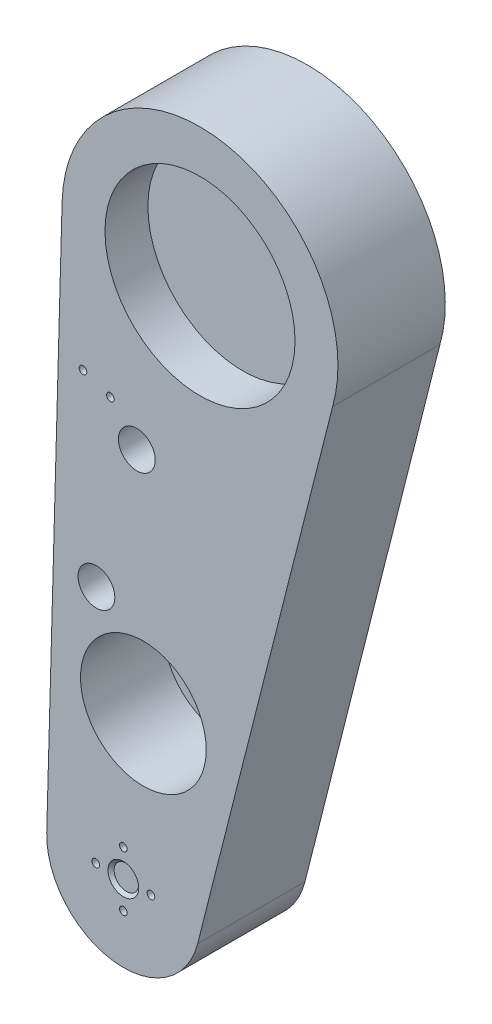
SolidWorks part; units mm, degrees
ref_plane "Ebene vorne" through (0, 0, 0) normal (0, 0, 1) x (1, 0, 0)
ref_plane "Ebene oben" through (0, 0, 0) normal (0, 1, 0) x (1, 0, 0)
ref_plane "Ebene rechts" through (0, 0, 0) normal (1, 0, 0) x (0, 0, -1)
sketch "Skizze1" plane through (0, 0, 0) normal (0, 0, 1) x (1, 0, 0)
  line L0 (-24.9904, 0.6931) -> (-19.9827, 181.2476)
  line L2 (68.9493, 170.3326) -> (24.2342, -6.1405)
  circle A0 centre (0, 0) radius 9
  circle A6 centre (0, 0) radius 25
  circle A7 centre (25, 180) radius 45
  circle A8 centre (25, 180) radius 28
  point P8 (0, 0)
  point P11 (-25, 0)
  point P12 (68.9493, 170.3326)
  point P14 (0, 0)
  dimension "D1" = 18
  dimension "D3" = 50
  dimension "D5" = 90
  dimension "D7" = 56
  dimension "D4" = 180
  dimension "D6" = 25
extrude "Aufsatz-Linear austragen1" add sketch "Skizze1" along normal blind 35 contours A7 | A7 A6 | A6 A0 | A0 | A7 region at (11.8715, 85.5396, 0) region at (0.3368, 24.2906, 0) region at (68.6084, 168.9504, 0) region at (0, 0, 0)
sketch "Skizze2" plane through (0, 0, 35) normal (0, 0, 1) x (1, 0, 0)
  circle A0 centre (0, 0) radius 4
  dimension "D1" = 8
extrude "Schnitt-Linear austragen1" cut sketch "Skizze2" against normal blind 1 contours A0
chamfer "Fase1" distance 1 angle 45 1 edges at (4, 0, 35)
sketch "Skizze3" plane through (0, 0, 35) normal (0, 0, 1) x (1, 0, 0)
sketch "Skizze4" plane through (0, 0, 35) normal (0, 0, 1) x (1, 0, 0)
  arc A0 (-1.247, 8.9132) -> (-8.9132, 1.247) centre (0, 0) ccw
  circle A1 centre (9, 0) radius 1.25
  circle A2 centre (0, -9) radius 1.25
  circle A3 centre (-9, 0) radius 1.25
  circle A4 centre (0, 9) radius 1.25
  arc A5 (-8.9132, -1.247) -> (-1.247, -8.9132) centre (0, 0) ccw
  arc A6 (8.9132, 1.247) -> (1.247, 8.9132) centre (0, 0) ccw
  arc A7 (1.247, -8.9132) -> (8.9132, -1.247) centre (0, 0) ccw
  point P14 (0, 0)
  dimension "D1" = 18
  dimension "D2" = 4
  dimension "D3" = 2.5
extrude "Schnitt-Linear austragen2" cut sketch "Skizze4" against normal blind 15 contours A4 | A1 | A2 | A3 region at (0, 9, 35) region at (-9, 0, 35) region at (9, 0, 35) region at (0, -9, 35)
sketch "Skizze5" plane through (0, 0, 0) normal (0, 0, -1) x (-1, 0, 0)
  circle A0 centre (0, 0) radius 8
  circle A1 centre (8, 0) radius 1.25
  circle A2 centre (0, -8) radius 1.25
  circle A3 centre (-8, 0) radius 1.25
  circle A4 centre (0, 8) radius 1.25
  circle A5 centre (0, 0) radius 9.25
  point P14 (0, 0)
  dimension "D1" = 4
  dimension "D3" = 16
extrude "Schnitt-Linear austragen3" cut sketch "Skizze5" against normal blind 15 contours A0 A4 | A0 A4 | A0 A3 | A0 A3 | A0 A1 | A0 A1 | A0 A2 | A0 A2 region at (-7.4523, 0, 0) region at (-8.5125, 0, 0) region at (0, 7.4523, 0) region at (0, 8.5125, 0) region at (0, -8.5125, 0) region at (0, -7.4523, 0) region at (7.4523, 0, 0) region at (8.5125, 0, 0)
sketch "Skizze6" plane through (0, 0, 35) normal (0, 0, 1) x (1, 0, 0)
  line L1 (25, 182.9902) -> (0, 2.9902) construction
  circle A1 centre (6.5291, 50) radius 12.5
  point P5 (0, 0)
  point P11 (0, 0)
  point P12 (0, 0)
  point P13 (0, 0)
  point P14 (0, 0)
  dimension "D1" = 50
  dimension "D2" = 25
extrude "Schnitt-Linear austragen4" cut sketch "Skizze6" against normal blind 35
sketch "Skizze7" plane through (0, 0, 35) normal (0, 0, 1) x (1, 0, 0)
  circle A0 centre (6.5291, 50) radius 20.5
  dimension "D1" = 41
extrude "Schnitt-Linear austragen5" cut sketch "Skizze7" against normal offset from surface (27 mm away) 8 up to face at (19.0291, 50, 0)
sketch "Skizze8" plane through (0, 0, 8) normal (0, 0, 1) x (1, 0, 0)
  line L0 (6.5291, 50) -> (5.2968, 32.5434) construction
  arc A0 (5.7616, 67.4832) -> (-10.6728, 53.216) centre (6.5291, 50) ccw
  circle A1 centre (5.2968, 32.5434) radius 2
  circle A2 centre (-10.9274, 51.2323) radius 2
  circle A3 centre (7.7615, 67.4566) radius 2
  circle A4 centre (23.9857, 48.7677) radius 2
  arc A5 (24.0123, 50.7675) -> (9.7452, 67.2019) centre (6.5291, 50) ccw
  arc A6 (7.2966, 32.5168) -> (24.0123, 50.7675) centre (6.5291, 50) ccw
  arc A7 (-10.6728, 53.216) -> (3.3131, 32.7981) centre (6.5291, 50) ccw
  point P14 (6.5291, 50)
  dimension "D1" = 4
  dimension "D2" = 4
  dimension "D3" = 17.5
extrude "Schnitt-Linear austragen6" cut sketch "Skizze8" against normal blind 15 contours A4 | A3 | A1 | A2 | A2 | A4 region at (7.7615, 67.4566, 8) region at (-11.7533, 51.2906, 8) region at (23.1188, 48.8289, 8) region at (5.2968, 32.5434, 8)
sketch "Skizze9" plane through (0, 0, 0) normal (0, 0, -1) x (-1, 0, 0)
  circle A0 centre (-5.2968, 32.5434) radius 3.5
  circle A1 centre (-23.9857, 48.7677) radius 3.5
  circle A2 centre (-7.7615, 67.4566) radius 3.5
  circle A3 centre (10.9274, 51.2323) radius 3.5
  point P3 (-6.5291, 50)
  point P14 (-6.5291, 50)
  dimension "D1" = 7
  dimension "D2" = 4
extrude "Schnitt-Linear austragen7" cut sketch "Skizze9" against normal blind 4
sketch "Skizze10" plane through (0, 0, 35) normal (0, 0, 1) x (1, 0, 0)
  circle A0 centre (25, 180) radius 31
  dimension "D1" = 62
extrude "Schnitt-Linear austragen8" cut sketch "Skizze10" against normal blind 14
ref_plane "Ebene1" through (0, 0, 17.5) normal (0, 0, 1) x (1, 0, 0)
mirror "Spiegeln1" about plane through (0, 0, 17.5) normal (0, 0, 1) of "Schnitt-Linear austragen8"
sketch "Skizze11" plane through (0, 0, 0) normal (0, 0, 1) x (1, 0, 0)
  circle A1 centre (25.3541, 102.1802) radius 1.65
extrude "Schnitt-Linear austragen10" cut sketch "Skizze11" along normal blind 15
sketch "Skizze12" plane through (0, 0, 0) normal (0, 0, -1) x (-1, 0, 0)
  circle A1 centre (-25, 180) radius 32
  circle A4 centre (-9.1089, 136.6817) radius 2.1
  dimension "D3" = 64
extrude "Schnitt-Linear austragen11" cut sketch "Skizze12" against normal blind 15 contours A4 region at (9.1089, 136.6817, 0)
sketch "Sketch1" plane through (0, 0, 0) normal (0, 0, -1) x (-1, 0, 0)
  line L0 (-13.9792, 149.9577) -> (-5.0749, 153.2242) construction
  line L1 (-5.0749, 153.2242) -> (-22.2848, 146.9108) construction
  line L2 (-20.8178, 148.2745) -> (-16.2029, 135.6945)
  line L3 (-16.2029, 135.6945) -> (-25.776, 148.0094)
  line L4 (-25, 180) -> (-2.3558, 118.273) construction
  line L5 (-7.6743, 153.0961) -> (-3.0594, 140.5161)
  line L6 (-3.0594, 140.5161) -> (-3.721, 156.1001)
  circle A0 centre (-25, 180) radius 32
  point P9 (-2.3558, 118.273)
  dimension "D1" = 64
  dimension "D2" = 14
extrude "Boss-Extrude1" add sketch "Sketch1" along normal blind 5 contours A0 L3 L2 | A0 L5 L6 region at (20.9083, 143.9511, 0) region at (4.8096, 149.8568, 0)
sketch "Sketch2" plane through (0, 0, 0) normal (0, 0, -1) x (-1, 0, 0)
  circle A0 centre (-4.4016, 123.4949) radius 6
  point P2 (-3.537, 124.4087)
  point P3 (-4.4016, 123.4949)
extrude "Cut-Extrude1" cut sketch "Sketch2" against normal blind 35
ref_plane "Plane1" through (0, 0, 30) normal (0, 0, -1) x (-1, 0, 0)
sketch "Sketch3" plane through (0, 0, 17.5) normal (0, 0, -1) x (-1, 0, 0)
  line L0 (14.468, 79.7139) -> (1.3635, 125.1573)
  line L1 (-10.1667, 121.8324) -> (2.9378, 76.3889)
  circle A0 centre (-4.4016, 123.4949) radius 6 construction
  circle A1 centre (-4.4016, 123.4949) radius 6
  circle A2 centre (8.7029, 78.0514) radius 6
  point P9 (11.3795, 73.7481)
  point P12 (8.9095, 77.3348)
  dimension "D1" = 12
extrude "Cut-Extrude2" cut sketch "Sketch3" along normal blind 8 contours A2 L0 L1 | A2 region at (-2.1506, 100.7731, 17.5) region at (-8.7029, 78.0514, 17.5)
sketch "Sketch4" plane through (0, 0, 35) normal (0, 0, 1) x (1, 0, 0)
  circle A2 centre (-8.7869, 78.1376) radius 6
  point P2 (-10.0844, 77.8404)
  point P3 (-9.8366, 76.8398)
  point P4 (-9.7227, 80.5162)
  point P5 (-8.585, 79.096)
  point P6 (-8.6275, 77.6631)
  point P7 (-8.7732, 77.1545)
  point P8 (-8.6549, 77.8615)
  point P9 (-8.682, 78.2646)
  point P10 (-8.7869, 78.1376)
extrude "Cut-Extrude3" cut sketch "Sketch4" against normal up to surface (25.5 mm away) up to face at (-2.9819, 97.8906, 9.5)
sketch "Skizze14" plane through (0, 0, 0) normal (0, 0, -1) x (-1, 0, 0)
  circle A0 centre (-59.0996, 191.6681) radius 1.65
  circle A1 centre (4.4449, 200.7123) radius 1.655
  circle A2 centre (-26.5283, 29.0181) radius 1.65
  circle A3 centre (18.5472, 35.4337) radius 1.65
extrude "Schnitt-Linear austragen12" cut sketch "Skizze14" against normal blind 15
sketch "Skizze16" plane through (0, 0, 35) normal (0, 0, 1) x (1, 0, 0)
  circle A3 centre (-13.1725, 137.1867) radius 1.25
  circle A4 centre (-4.2165, 134.0181) radius 1.25
extrude "Schnitt-Linear austragen14" cut sketch "Skizze16" against normal blind 6
sketch "Skizze13" plane through (0, 0, 0) normal (0, 0, -1) x (-1, 0, 0)
  circle A3 centre (-16.0818, 52.3597) radius 1.65
  circle A4 centre (-53.8461, 158.4958) radius 1.65
  circle A5 centre (4.4913, 200.5829) radius 1.65
